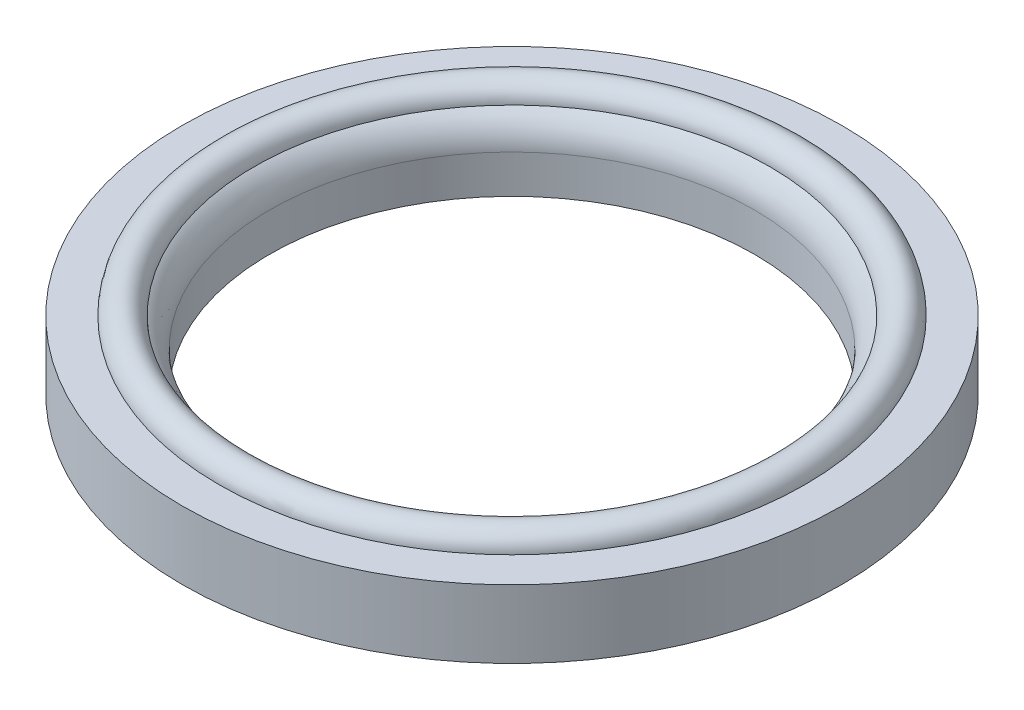
SolidWorks part; units mm, degrees
material "ABS"
ref_plane "Front" through (0, 0, 0) normal (0, 0, 1) x (1, 0, 0)
ref_plane "Top" through (0, 0, 0) normal (0, 1, 0) x (1, 0, 0)
ref_plane "Right" through (0, 0, 0) normal (1, 0, 0) x (0, 0, -1)
ref_axis "Axis1" through (0, 0, 55) along (0, 0, -1)
sketch "Sketch1" plane through (0, 0, 0) normal (0, 1, 0) x (1, 0, 0)
  circle A0 centre (0, 0) radius 23.0505
  circle A1 centre (0, 0) radius 16.9545
  dimension "D1" = 46.101
  dimension "D2" = 6.096
extrude "Boss-Extrude1" add sketch "Sketch1" along normal blind 4.7625
sketch "Sketch2" plane through (0, 0, 0) normal (0, 0, 1) x (1, 0, 0)
  line L0 (18.034, 4.7104) -> (20.4773, 4.74)
  line L1 (0, 0) -> (0, 20.6153) construction
  arc A0 (18.034, 4.7104) -> (20.4773, 4.74) centre (19.2557, 4.7252) cw
  dimension "D1" = 1.2217
  dimension "D2" = 18.034
  dimension "D3" = 19.2557
  dimension "D4" = 4.7104
revolve "Revolve1" add sketch "Sketch2" angle 360 about L1
fillet "Fillet1" radius 2.54 1 edges at (0, 4.7625, 16.9545)
